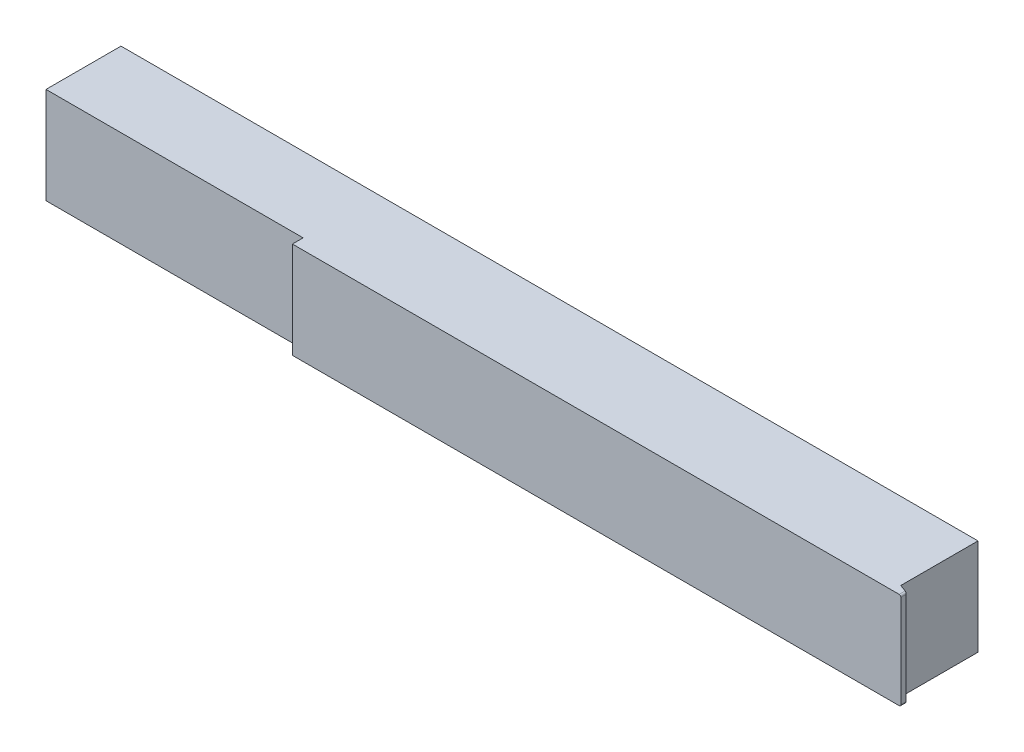
SolidWorks part; units mm, degrees
ref_plane "Front Plane" through (0, 0, 0) normal (1, 0, 0) x (0, 1, 0)
ref_plane "Top Plane" through (0, 0, 0) normal (0, 0, 1) x (0, 1, 0)
ref_plane "Right Plane" through (0, 0, 0) normal (0, 1, 0) x (-1, 0, 0)
sketch "Sketch1" plane through (0, 0, 0) normal (0, 0, 1) x (0, 1, 0)
  line L1 (0, 0) -> (22.5, 0)
  line L2 (0, 0) -> (0, -202)
  line L3 (0, -202) -> (22.5, -202)
  line L4 (22.5, 0) -> (22.5, -202)
extrude "Boss-Extrude1" add sketch "Sketch1" against normal blind 20 contours L2 L3 L4 L1
sketch "Sketch2" plane through (202, 0, 0) normal (1, 0, 0) x (0, 1, 0)
  line L0 (22.5, -20) -> (22.5, 0) construction
  line L1 (0, -20) -> (22.5, -20)
  line L2 (0, -20) -> (0, -2)
  line L3 (0, -2) -> (22.5, -2)
  line L4 (22.5, -20) -> (22.5, -2)
extrude "Cut-Extrude1" cut sketch "Sketch2" against normal blind 2 contours L3 L4 L1 L2
chamfer "Chamfer5" distance 0.75 angle 70 1 edges at (202, 11.25, -2) first distance on face at (202, 11.25, -1)
fillet "Fillet5" radius 0.4 2 edges at (202, 0, -0.625) (202, 22.5, -0.625)
sketch "Sketch3" plane through (0, 22.5, 0) normal (0, 1, 0) x (-1, 0, 0)
  line L0 (0, 0) -> (-201.6, 0) construction
  line L1 (-200, -20) -> (-60, -20)
  line L2 (-200, -20) -> (-200, 0)
  line L3 (-200, 0) -> (-60, 0)
  line L4 (-60, -20) -> (-60, 0)
  line L5 (0, -20) -> (0, 0) construction
  line L6 (-60, -20) -> (0, -20)
  line L7 (-60, -20) -> (-60, -10)
  line L8 (-60, -10) -> (0, -10)
  line L9 (0, -20) -> (0, -10)
  line L11 (-60, 0) -> (0, 0)
  line L12 (-60, 0) -> (-60, -2.5)
  line L17 (-60, -2.5) -> (0, -2.5)
  line L18 (0, 0) -> (0, -2.5)
extrude "Cut-Extrude2" cut sketch "Sketch3" against normal up to surface (22.5 mm away) contours L12 L17 L18 L11 up to face at (133.8667, 0, -7.2289)
sketch3d "3DSketch1" plane through (0, 0, 0) normal (0, 0, 1) x (1, 0, 0)
  dimension "D1" = 11.25
sketch "Sketch4" plane through (0, 11.25, 0) normal (0, 1, 0) x (1, 0, 0)
  line L0 (60, 20) -> (195, 20)
  line L1 (200, 20) -> (60, 20) construction
  line L2 (195, 20) -> (195, 7.5)
  line L3 (195, 7.5) -> (60, 20)
  dimension "D1" = 12.5
  dimension "D2" = 135
sketch "Sketch5" plane through (0, 22.5, 0) normal (0, 1, 0) x (-1, 0, 0)
  line L1 (-60, -20) -> (-55, -20)
  line L2 (-60, -20) -> (-60, -15)
  line L3 (-60, -15) -> (-55, -15)
  line L4 (-55, -20) -> (-55, -15)
  circle A0 centre (-60, -15) radius 2.5
extrude "Cut-Extrude3" [suppressed] cut sketch "Sketch5" against normal through all contours A0
